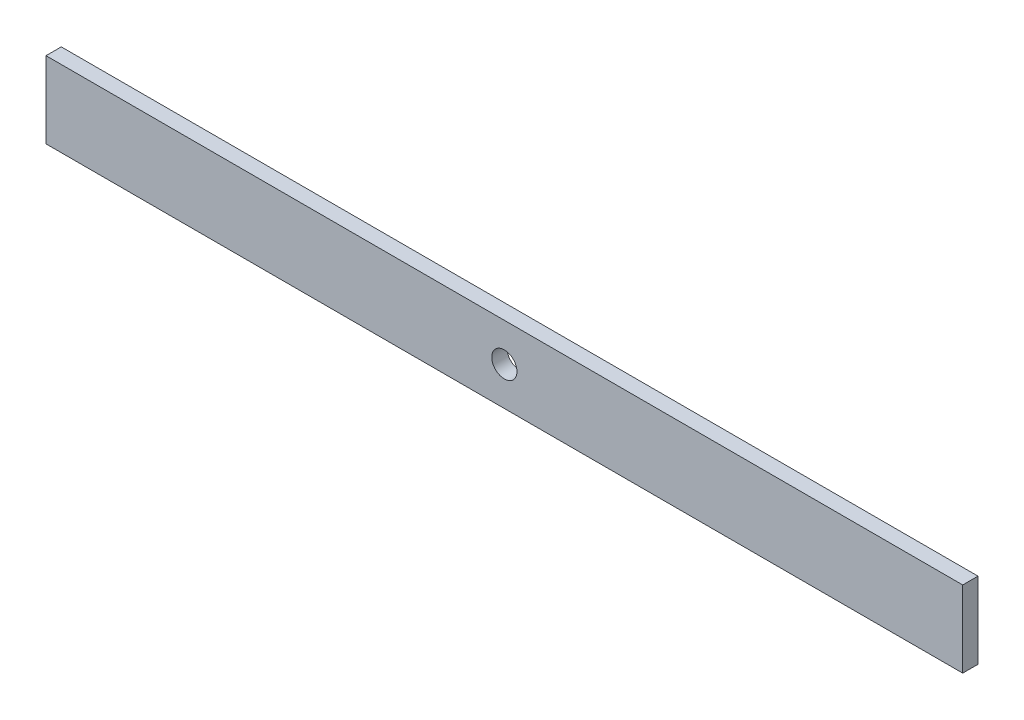
SolidWorks part; units mm, degrees
material "AISI 1020"
ref_plane "Plano frontal" through (0, 0, 0) normal (0, 0, 1) x (1, 0, 0)
ref_plane "Plano superior" through (0, 0, 0) normal (0, 1, 0) x (1, 0, 0)
ref_plane "Plano direito" through (0, 0, 0) normal (1, 0, 0) x (0, 0, -1)
sketch "Esboço1" plane through (0, 0, 0) normal (0, 0, 1) x (1, 0, 0)
  line L1 (-60, 5) -> (60, 5)
  line L2 (-60, 5) -> (-60, -5)
  line L3 (-60, -5) -> (60, -5)
  line L4 (60, 5) -> (60, -5)
  line L5 (-60, 5) -> (60, -5) construction
  line L6 (-60, -5) -> (60, 5) construction
  point P0 (0, 0)
  dimension "D1" = 120
  dimension "D2" = 10
base flange "Flange-base1" sketch "Esboço1" thickness 2 reverse thickness direction no parameters "D1"=2.7366
hole_wizard "Broca de rosquear de cano para tarraxa de 1/81" positions "Esboço7" profile "Esboço8" hole size "1/8" standard "Ansi Inch"
sketch "Esboço7" plane through (0, 0, -2) normal (0, 0, -1) x (-1, 0, 0)
  point P0 (0, 0)
sketch "Esboço8" plane through (0, 0, -2) normal (1, 0, 0) x (0, 1, 0)
  line L0 (0, 0) -> (0, 4.9914)
  line L1 (0, 4.9914) -> (1.65, 4)
  line L2 (1.65, 4) -> (1.65, 0)
  line L5 (1.65, 0) -> (0, 0)
  line L10 (0, 4.9914) -> (-1.65, 4) construction
  line L11 (0, -6.35) -> (0, 107.95) construction
  dimension "Hole Dia." = 3.3
  dimension "Hole Depth" = 4
  dimension "Drill Angle" = 118
sketch "Curva-Linhas1" [suppressed] plane through (0, 0, 0) normal (0, 1, 0) x (1, 0, 0)
sketch "Caixa delimitadora1" [suppressed] plane through (0, 0, 0) normal (0, 1, 0) x (1, 0, 0)
sheet metal parameters "Chapa metálica1" thickness 2 parameters "D1"=2.7366
flat pattern "Padrão-Plano1" [suppressed]
sketch "Curva-Linhas2" plane through (0, 0, 0) normal (0, 0, 1) x (1, 0, 0)
  line L0 (48.3562, -2.5) -> (48.3562, 2.5) construction
  line L1 (-48.3562, 2.5) -> (-48.3562, -2.5) construction
  line L2 (48.3562, -2.5) -> (48.3562, 2.5) construction
  line L3 (-48.3562, 2.5) -> (-48.3562, -2.5) construction
sketch3d "Caixa delimitadora2" [suppressed]
  line L0 (-60, -2.5, 0) -> (60, -2.5, 0) construction
  line L1 (-60, 2.5, 0) -> (60, 2.5, 0) construction
  line L2 (-60, -2.5, 0) -> (-60, 2.5, 0) construction
  line L3 (60, -2.5, 0) -> (60, 2.5, 0) construction
sheet metal parameters "Chapa metálica4" thickness 2 parameters "D1"=2.7366
flat pattern "Padrão-Plano1"
sketch "Curva-Linhas2" plane through (0, 0, 0) normal (0, 0, 1) x (1, 0, 0)
  point P0 (48.3562, -5)
  point P1 (48.3562, 5)
  point P2 (-48.3562, 5)
  point P3 (-48.3562, -5)
sketch3d "Caixa delimitadora2" [suppressed]
  line L0 (-60, -5, 0) -> (60, -5, 0) construction
  line L1 (-60, 5, 0) -> (60, 5, 0) construction
  line L2 (-60, -5, 0) -> (-60, 5, 0) construction
  line L3 (60, -5, 0) -> (60, 5, 0) construction
